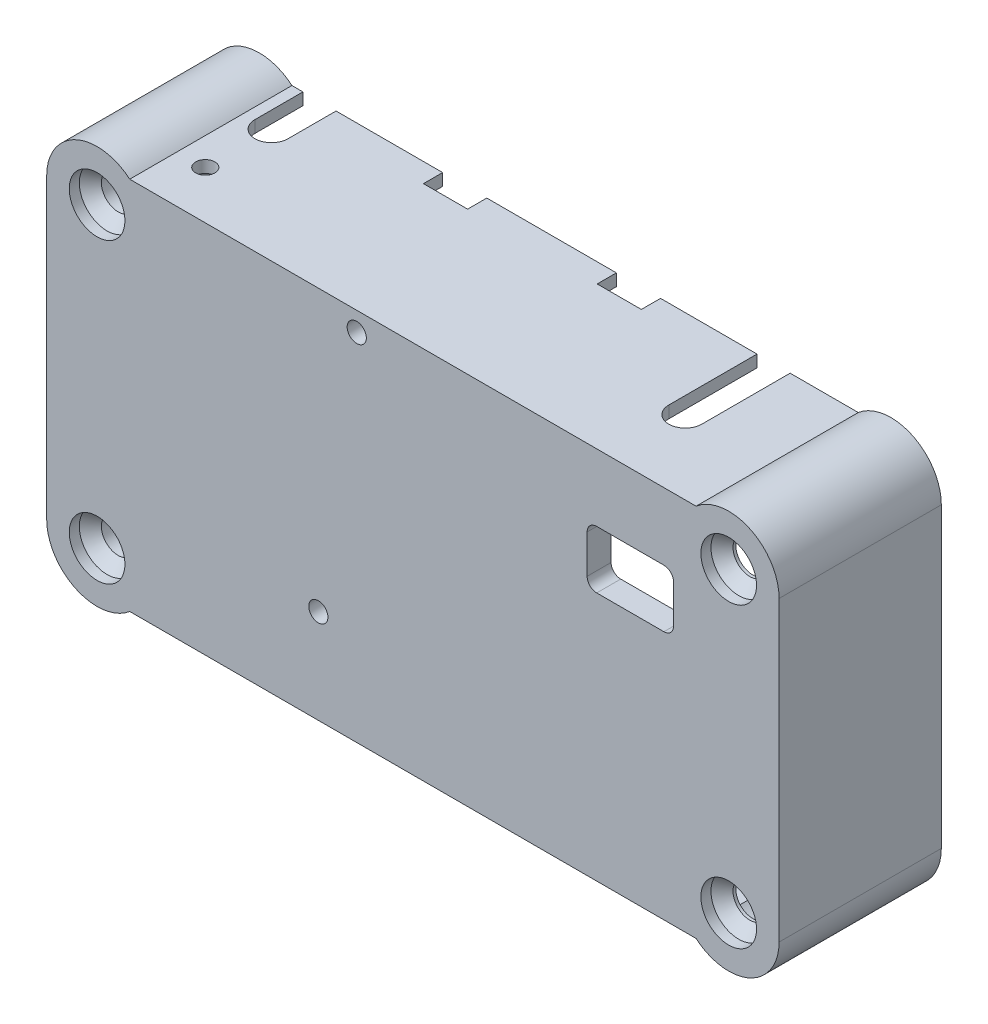
SolidWorks part; units mm, degrees
ref_plane "Front Plane" through (0, 0, 0) normal (0, 0, 1) x (1, 0, 0)
ref_plane "Top Plane" through (0, 0, 0) normal (0, 1, 0) x (1, 0, 0)
ref_plane "Right Plane" through (0, 0, 0) normal (1, 0, 0) x (0, 0, -1)
sketch "Sketch1" plane through (0, 0, 0) normal (0, 0, 1) x (1, 0, 0)
  line L0 (-29.7106, 19.8451) -> (30.4992, 19.8451)
  line L1 (-36.2557, 17.3451) -> (-36.2557, -13.6549)
  line L2 (-29.7106, -16.1549) -> (30.4992, -16.1549)
  line L3 (37.0443, 17.3451) -> (37.0443, -13.6549)
  circle A1 centre (-32.5057, 17.3451) radius 3.75
  arc A2 (-29.7106, 19.8451) -> (-36.2557, 17.3451) centre (-32.5057, 17.3451) ccw construction
  circle A3 centre (-32.5057, 17.3451) radius 1.75
  circle A4 centre (-32.5057, 17.3451) radius 1.75 construction
  circle A8 centre (-32.5057, -13.6549) radius 1.75
  circle A9 centre (-32.5057, -13.6549) radius 1.75 construction
  circle A10 centre (-32.5057, -13.6549) radius 3.75
  arc A11 (-36.2557, -13.6549) -> (-29.7106, -16.1549) centre (-32.5057, -13.6549) ccw construction
  circle A12 centre (33.2943, 17.3451) radius 3.75
  arc A13 (37.0443, 17.3451) -> (30.1222, 15.3451) centre (33.2943, 17.3451) ccw construction
  circle A14 centre (33.2943, 17.3451) radius 1.75
  circle A15 centre (33.2943, 17.3451) radius 1.75 construction
  circle A16 centre (33.2943, -13.6549) radius 3.75
  arc A17 (30.1222, -11.6549) -> (37.0443, -13.6549) centre (33.2943, -13.6549) ccw construction
  circle A18 centre (33.2943, -13.6549) radius 1.75
  circle A19 centre (33.2943, -13.6549) radius 1.75 construction
extrude "Boss-Extrude1" add sketch "Sketch1" along normal blind 2.5 contours A16 L3 A12 L0 A1 L1 A10 L2 | A1 A3 | A10 A8 | A12 A14 | A16 A18 region at (0.3943, 1.8451, 0) region at (-29.1016, 18.6453, 0) region at (34.5945, 20.7492, 0) region at (-32.5057, -10.011, 0) region at (34.5945, -17.059, 0)
sketch "Sketch2" plane through (0, 0, 2.5) normal (0, 0, 1) x (1, 0, 0)
  line L0 (-37.7557, 17.3451) -> (-37.7557, -13.6549)
  line L1 (-29.1053, -17.6549) -> (29.8939, -17.6549)
  line L2 (38.5443, -13.6549) -> (38.5443, 17.3451)
  line L3 (29.8939, 21.3451) -> (-29.1053, 21.3451)
  line L4 (-29.7106, -16.1549) -> (30.4992, -16.1549)
  line L5 (37.0443, -13.6549) -> (37.0443, 17.3451)
  line L6 (30.4992, 19.8451) -> (-29.7106, 19.8451)
  line L7 (-36.2557, 17.3451) -> (-36.2557, -13.6549)
  line L8 (-29.7106, -16.1549) -> (30.4992, -16.1549)
  line L9 (37.0443, -13.6549) -> (37.0443, 17.3451)
  line L10 (30.4992, 19.8451) -> (-29.7106, 19.8451)
  line L11 (-36.2557, 17.3451) -> (-36.2557, -13.6549)
  arc A0 (-29.1053, 21.3451) -> (-37.7557, 17.3451) centre (-32.5057, 17.3451) ccw
  arc A1 (-37.7557, -13.6549) -> (-29.1053, -17.6549) centre (-32.5057, -13.6549) ccw
  arc A2 (29.8939, -17.6549) -> (38.5443, -13.6549) centre (33.2943, -13.6549) ccw
  arc A3 (38.5443, 17.3451) -> (29.8939, 21.3451) centre (33.2943, 17.3451) ccw
  arc A4 (30.4992, -16.1549) -> (37.0443, -13.6549) centre (33.2943, -13.6549) ccw
  arc A5 (37.0443, 17.3451) -> (30.4992, 19.8451) centre (33.2943, 17.3451) ccw
  arc A6 (-29.7106, 19.8451) -> (-36.2557, 17.3451) centre (-32.5057, 17.3451) ccw
  arc A7 (-36.2557, -13.6549) -> (-29.7106, -16.1549) centre (-32.5057, -13.6549) ccw
  arc A8 (30.4992, -16.1549) -> (37.0443, -13.6549) centre (33.2943, -13.6549) ccw
  arc A9 (37.0443, 17.3451) -> (30.4992, 19.8451) centre (33.2943, 17.3451) ccw
  arc A10 (-29.7106, 19.8451) -> (-36.2557, 17.3451) centre (-32.5057, 17.3451) ccw
  arc A11 (-36.2557, -13.6549) -> (-29.7106, -16.1549) centre (-32.5057, -13.6549) ccw
  dimension "D1" = 0
  dimension "D2" = 1.5
extrude "Boss-Extrude2" add sketch "Sketch2" against normal up to surface (2.5 mm away) up to face at (0.3943, 1.8451, 0)
sketch "Sketch3" plane through (0, 0, 0) normal (0, 0, -1) x (-1, 0, 0)
  line L1 (29.601, 20.0951) -> (-30.3896, 20.0951)
  line L2 (-37.2943, 17.3451) -> (-37.2943, -13.6549)
  line L3 (-30.3896, -16.4049) -> (29.601, -16.4049)
  line L4 (29.1053, 21.3451) -> (-29.8939, 21.3451)
  line L5 (-38.5443, 17.3451) -> (-38.5443, -13.6549)
  line L6 (-29.8939, -17.6549) -> (29.1053, -17.6549)
  line L7 (37.7557, -13.6549) -> (37.7557, 17.3451)
  line L8 (29.1053, 21.3451) -> (-29.8939, 21.3451)
  line L9 (-38.5443, 17.3451) -> (-38.5443, -13.6549)
  line L10 (-29.8939, -17.6549) -> (29.1053, -17.6549)
  line L11 (37.7557, -13.6549) -> (37.7557, 17.3451)
  line L12 (36.5057, -13.6549) -> (36.5057, 17.3451)
  arc A1 (-30.3896, 20.0951) -> (-37.2943, 17.3451) centre (-33.2943, 17.3451) ccw
  arc A2 (-37.2943, -13.6549) -> (-30.3896, -16.4049) centre (-33.2943, -13.6549) ccw
  arc A3 (29.601, -16.4049) -> (36.5057, -13.6549) centre (32.5057, -13.6549) ccw
  arc A4 (37.7557, 17.3451) -> (29.1053, 21.3451) centre (32.5057, 17.3451) ccw
  arc A5 (-29.8939, 21.3451) -> (-38.5443, 17.3451) centre (-33.2943, 17.3451) ccw
  arc A6 (-38.5443, -13.6549) -> (-29.8939, -17.6549) centre (-33.2943, -13.6549) ccw
  arc A7 (29.1053, -17.6549) -> (37.7557, -13.6549) centre (32.5057, -13.6549) ccw
  arc A8 (37.7557, 17.3451) -> (29.1053, 21.3451) centre (32.5057, 17.3451) ccw
  arc A9 (-29.8939, 21.3451) -> (-38.5443, 17.3451) centre (-33.2943, 17.3451) ccw
  arc A10 (-38.5443, -13.6549) -> (-29.8939, -17.6549) centre (-33.2943, -13.6549) ccw
  arc A11 (29.1053, -17.6549) -> (37.7557, -13.6549) centre (32.5057, -13.6549) ccw
  arc A12 (36.5057, 17.3451) -> (29.601, 20.0951) centre (32.5057, 17.3451) ccw
  dimension "D1" = 0
  dimension "D2" = 1.25
extrude "Boss-Extrude3" add sketch "Sketch3" along normal up to surface (14.4 mm away)
sketch "Sketch8" plane through (0, 0, 0) normal (0, 0, -1) x (-1, 0, 0)
  line L0 (37.7557, 17.3451) -> (37.7557, -13.6549)
  line L1 (29.1053, 21.3451) -> (29.1053, -17.6549)
  circle A0 centre (32.5057, 17.3451) radius 5.25
  arc A1 (37.7557, 17.3451) -> (29.1053, 21.3451) centre (32.5057, 17.3451) ccw construction
  circle A2 centre (32.5057, 17.3451) radius 1.75
  circle A3 centre (32.5057, 17.3451) radius 1.75 construction
  circle A4 centre (32.5057, -13.6549) radius 5.25
  arc A5 (29.1053, -17.6549) -> (37.7557, -13.6549) centre (32.5057, -13.6549) ccw construction
  circle A6 centre (32.5057, -13.6549) radius 1.75
  circle A7 centre (32.5057, -13.6549) radius 1.75 construction
  circle M3 centre (32.5057, 17.3451) radius 1.75
  circle M4 centre (32.5057, -13.6549) radius 1.75
  arc M5 (29.601, -16.4049) -> (36.5057, -13.6549) centre (32.5057, -13.6549) ccw
  line M6 (36.5057, -13.6549) -> (36.5057, 17.3451)
  arc M7 (36.5057, 17.3451) -> (29.601, 20.0951) centre (32.5057, 17.3451) ccw
  line M8 (29.601, 20.0951) -> (-30.3896, 20.0951)
  line M12 (-30.3896, -16.4049) -> (29.601, -16.4049)
extrude "Boss-Extrude4" add sketch "Sketch8" along normal up to surface (6.75 mm away) contours L1 A0 M6 M7 M8 M3 | A4 A0 L1 M6 | A4 L1 M6 M12 M5 M4 region at (-32.835, 1.8451, 0) region at (-32.9201, 12.2303, 0) region at (-36.3872, -11.9547, 0)
sketch "Sketch4" plane through (-37.7557, 0, 0) normal (-1, 0, 0) x (0, 0, 1)
  line L12 (-11.9, -11.8549) -> (-3.3, -11.8549)
  line L13 (-3.3, -11.8549) -> (-3.3, 1.2216)
  line L14 (-3.3, 1.2216) -> (-6.0107, 4.2451)
  line L15 (-6.0107, 4.2451) -> (-9.1893, 4.2451)
  line L16 (-9.1893, 4.2451) -> (-11.9, 1.2216)
  line L17 (-11.9, 1.2216) -> (-11.9, -11.8549)
  line L18 (-11.9, -11.8549) -> (-3.3, -11.8549)
  line L19 (-3.3, -11.8549) -> (-3.3, 1.2216)
  line L20 (-3.3, 1.2216) -> (-6.0107, 4.2451)
  line L21 (-6.0107, 4.2451) -> (-9.1893, 4.2451)
  line L22 (-9.1893, 4.2451) -> (-11.9, 1.2216)
  line L23 (-11.9, 1.2216) -> (-11.9, -11.8549)
  dimension "D1" = 0.2
extrude "Cut-Extrude1" cut sketch "Sketch4" against normal up to next
sketch "Sketch5" plane through (0, 21.3451, 0) normal (0, 1, 0) x (1, 0, 0)
  line L0 (-27.9607, 9.4) -> (-27.9607, 14.4)
  line L1 (-29.1053, 14.4) -> (29.8939, 14.4) construction
  line L2 (-24.5107, 9.4) -> (-24.5107, 14.4)
  line L3 (-24.5107, 14.4) -> (-27.9607, 14.4)
  line L4 (19.3445, 5.2047) -> (19.3445, 14.4)
  line L5 (22.7945, 5.2047) -> (22.7945, 14.4)
  circle A1 centre (21.0695, 5.2047) radius 1.725
  circle A2 centre (-26.2357, 9.4) radius 1.725
  circle A3 centre (-26.2357, 9.4) radius 1.725
  circle A4 centre (21.0695, 5.2047) radius 0.95 construction
  point P15 (0, 0)
  point P16 (0, 0)
  point P17 (20.394, 7.7086)
  line M3 (29.8939, 14.4) -> (-29.1053, 14.4)
  dimension "D1" = 0.5
extrude "Cut-Extrude2" cut sketch "Sketch5" against normal up to next contours A3 | A3 L2 L0 M3 | A1 L5 L4 M3 | A1 region at (21.0695, 21.3451, -10.4703) region at (-26.2357, 21.3451, -12.5571) region at (-26.2357, 21.3451, -9.4) region at (21.0695, 21.3451, -5.2047)
sketch "Sketch6" plane through (0, 21.3451, 0) normal (0, 1, 0) x (1, 0, 0)
  line L0 (-26.2357, 7.675) -> (-26.2357, -2.5) construction
  line L1 (29.8939, -2.5) -> (-29.1053, -2.5) construction
  arc A0 (-27.9607, 9.4) -> (-24.5107, 9.4) centre (-26.2357, 9.4) ccw construction
  circle A1 centre (-26.2357, 2.5) radius 1
  dimension "D1" = 2
  dimension "D2" = 5
extrude "Cut-Extrude3" cut sketch "Sketch6" against normal through all
sketch "Sketch7" plane through (0, 0, 2.5) normal (0, 0, 1) x (1, 0, 0)
  line L1 (27.5443, 8.3451) -> (18.5443, 8.3451)
  line L2 (27.5443, 8.3451) -> (27.5443, 14.3451)
  line L3 (27.5443, 14.3451) -> (18.5443, 14.3451)
  line L4 (18.5443, 8.3451) -> (18.5443, 14.3451)
  line L6 (38.5443, -13.6549) -> (38.5443, 17.3451) construction
  line L7 (29.8939, 21.3451) -> (-29.1053, 21.3451) construction
  line L8 (-3.2057, 19.3451) -> (-3.2057, 21.3451) construction
  line L9 (-7.7057, 19.3451) -> (-7.7057, 21.3451) construction
  line L10 (-3.2057, 18.0451) -> (-3.2057, 19.8451) construction
  line L11 (-7.7057, 18.0451) -> (-7.7057, 19.8451) construction
  circle A0 centre (-9.4557, -7.8549) radius 1
  circle A1 centre (-5.4557, 19.3451) radius 2.25
  circle A2 centre (-9.4557, -7.8549) radius 0.875 construction
  circle A3 centre (-5.4557, 19.3451) radius 1
  dimension "D5" = 2
  dimension "D6" = 2
  dimension "D1" = 11
  dimension "D2" = 7
  dimension "D3" = 6
  dimension "D4" = 9
extrude "Cut-Extrude4" cut sketch "Sketch7" against normal up to next contours L4 L1 L2 L3 | A3 | A0 region at (23.0443, 11.3451, 2.5) region at (-9.4557, -7.8549, 2.5) region at (-5.4557, 19.3451, 2.5)
sketch "Sketch9" plane through (0, 0, 2.5) normal (0, 0, 1) x (1, 0, 0)
  circle A0 centre (-32.5057, 17.3451) radius 2.9
  circle A1 centre (33.2943, 17.3451) radius 2.9
  circle A2 centre (33.2943, -13.6549) radius 2.9
  circle A3 centre (-32.5057, -13.6549) radius 2.9
  dimension "D1" = 5.8
extrude "Cut-Extrude5" cut sketch "Sketch9" against normal blind 0.2
chamfer "Chamfer1" distance 2 angle 45 4 edges at (35.0443, -13.6549, 2.3) (35.0443, 17.3451, 2.3) (-30.7557, -13.6549, 2.3) (-30.7557, 17.3451, 2.3)
sketch "Sketch10" plane through (0, 21.3451, 0) normal (0, 1, 0) x (1, 0, 0)
  line L0 (-24.5107, 14.4) -> (19.3445, 14.4) construction
  line L1 (9.2943, 14.4) -> (4.6943, 14.4)
  line L2 (9.2943, 14.4) -> (9.2943, 12.4)
  line L3 (9.2943, 12.4) -> (4.6943, 12.4)
  line L4 (4.6943, 14.4) -> (4.6943, 12.4)
  line L5 (9.2943, 13.7) -> (9.2943, 11.9) construction
  line L6 (4.6943, 13.7) -> (4.6943, 11.9) construction
  line L7 (-8.8057, 13.7) -> (-8.8057, 11.9) construction
  line L8 (-8.8057, 14.4) -> (-13.4057, 14.4)
  line L9 (-8.8057, 14.4) -> (-8.8057, 12.4)
  line L10 (-8.8057, 12.4) -> (-13.4057, 12.4)
  line L11 (-13.4057, 14.4) -> (-13.4057, 12.4)
  line L12 (-13.4057, 13.7) -> (-13.4057, 11.9) construction
  dimension "D1" = 2
extrude "Cut-Extrude6" cut sketch "Sketch10" against normal through all
fillet "Fillet1" radius 1 4 edges at (27.5443, 14.3451, 1.25) (27.5443, 8.3451, 1.25) (18.5443, 8.3451, 1.25) (18.5443, 14.3451, 1.25)
sketch "Sketch11" plane through (0, 0, -3.3) normal (0, 0, -1) x (-1, 0, 0)
  line L0 (29.1053, -5.3166) -> (36.5057, -5.3166) construction
  line L1 (29.1053, 1.2216) -> (29.1053, -11.8549) construction
  line L2 (36.5057, -13.6549) -> (36.5057, 17.3451) construction
  line L3 (29.1053, 1.2216) -> (37.7557, 1.2216) construction
  line L4 (32.5555, 1.2216) -> (33.0555, 1.2216)
  line L5 (32.5555, 1.2216) -> (32.5555, -11.8549)
  line L6 (32.5555, -11.8549) -> (33.0555, -11.8549)
  line L7 (33.0555, 1.2216) -> (33.0555, -11.8549)
  line L8 (32.5555, 1.2216) -> (33.0555, -11.8549) construction
  line L9 (32.5555, -11.8549) -> (33.0555, 1.2216) construction
  point P6 (32.8055, -5.3166)
  dimension "D1" = 0.5
extrude "Boss-Extrude5" add sketch "Sketch11" along normal blind 0.25
